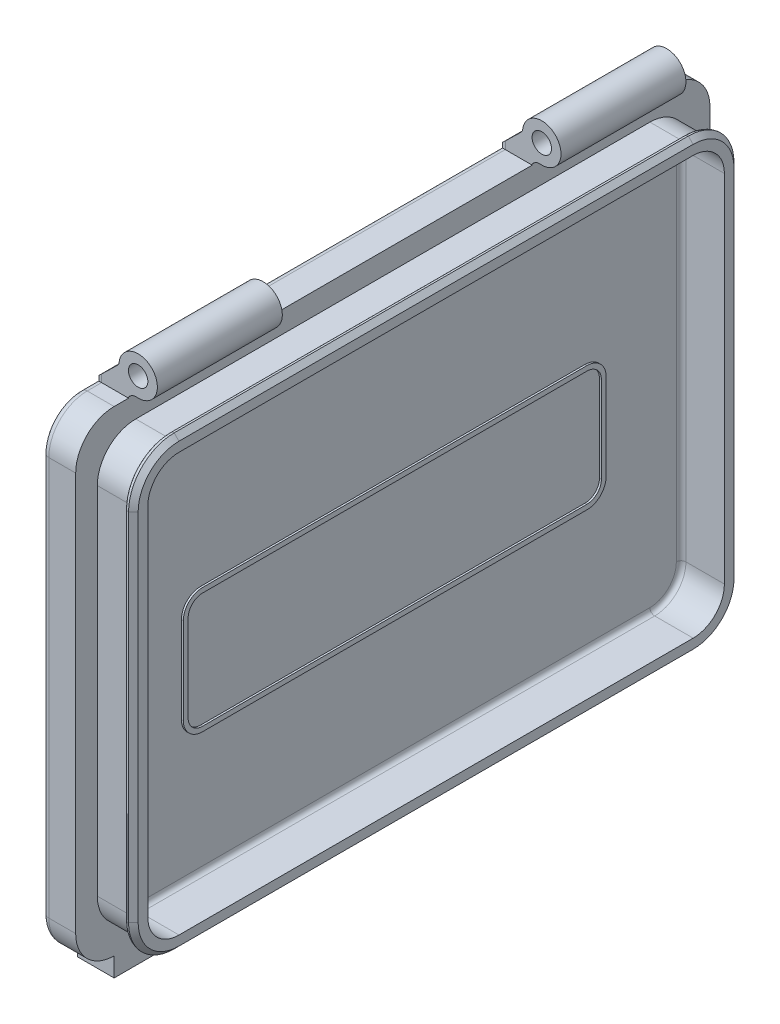
SolidWorks part; units mm, degrees
ref_plane "Front Plane" through (0, 0, 0) normal (0, 0, 1) x (1, 0, 0)
ref_plane "Top Plane" through (0, 0, 0) normal (0, 1, 0) x (1, 0, 0)
ref_plane "Right Plane" through (0, 0, 0) normal (1, 0, 0) x (0, 0, -1)
sketch "Sketch1" plane through (0, 0, 0) normal (0, 0, 1) x (1, 0, 0)
  circle A0 centre (0, 0) radius 1
  dimension "D1" = 2
extrude "Boss-Extrude1" add sketch "Sketch1" along normal blind 27.5
sketch "Sketch2" plane through (0, 0, 27.5) normal (0, 0, 1) x (1, 0, 0)
  line L0 (0, -1) -> (0, -2.4) construction
  line L1 (0, -2.4) -> (-1, -2.4) construction
  line L2 (-1, -2.4) -> (-4.5, -2.4) construction
  line L3 (-2.1365, -0.0921) -> (-4.5, -2.4)
  line L4 (-4.5, -2.4) -> (-1, -2.4)
  arc A0 (0, -2) -> (-1.9887, 0.2125) centre (0, 0) ccw
  circle A1 centre (0, 0) radius 1 construction
  arc A2 (-1, -2.4) -> (0, -2) centre (-0.1964, -2.9589) cw
  arc A3 (-2.1365, -0.0921) -> (-1.9887, 0.2125) centre (-2.4858, 0.2656) ccw
  circle A4 centre (0, 0) radius 1.01
  dimension "D1" = 4
  dimension "D5" = 0.5
  dimension "D6" = 2.02
  dimension "D2" = 1.4
  dimension "D3" = 1
  dimension "D4" = 3.5
extrude "Boss-Extrude2" add sketch "Sketch2" against normal blind 13 separate body
sketch "Sketch3" plane through (0, -2.4, 0) normal (0, -1, 0) x (1, 0, 0)
  line L0 (-4.5, 14.5) -> (-1, 14.5) construction
  line L1 (-4.5, 27.5) -> (-1, 27.5)
  line L2 (-4.5, 27.5) -> (-4.5, 14.5)
  line L3 (-4.5, 14.5) -> (-1, 14.5)
  line L4 (-1, 27.5) -> (-1, 14.5)
extrude "Boss-Extrude3" add sketch "Sketch3" along normal blind 49.6
sketch "Sketch7" plane through (0, 0, 27.5) normal (0, 0, 1) x (1, 0, 0)
  line L1 (-1, -52) -> (-1, -2.4) construction
  line L2 (-1, -2.5) -> (-4.5, -2.5)
  line L3 (-4.5, -52) -> (-4.5, -2.4) construction
  line L4 (-4.5, -2.5) -> (-4.5, -52)
  line L5 (-4.5, -52) -> (-1, -52)
  line L6 (-1, -52) -> (-1, -2.5)
extrude "Boss-Extrude6" add sketch "Sketch7" along normal blind 5.5
sketch "Sketch8" plane through (0, 0, 14.5) normal (0, 0, -1) x (-1, 0, 0)
  line L0 (4.5, -2.5) -> (1, -2.5)
  line L1 (1, -2.5) -> (1, -52)
  line L2 (1, -52) -> (4.5, -52)
  line L3 (4.5, -52) -> (4.5, -2.5)
extrude "Boss-Extrude7" add sketch "Sketch8" along normal blind 14.5
fillet "Fillet2" radius 4 2 edges at (-2.75, -52, 33) (-2.75, -2.5, 33)
ref_plane "Plane1" through (0, 0, 0) normal (0, 0, -1) x (-1, 0, 0)
sketch "Sketch10" plane through (0, 0, 0) normal (0, 0, -1) x (-1, 0, 0)
  line L0 (1, -52) -> (1, -54)
  line L1 (1, -54) -> (4.8, -54)
  line L2 (4.8, -54) -> (4.8, -53)
  line L3 (4.8, -53) -> (3.8, -53)
  line L4 (3.8, -53) -> (3.8, -52)
  line L5 (1, -52) -> (4.5, -52) construction
  line L6 (3.8, -52) -> (1, -52)
  line L7 (1, -52) -> (1.002, -52.0348)
  dimension "D1" = 2
  dimension "D2" = 3.8
  dimension "D3" = 1
  dimension "D4" = 1
extrude "Boss-Extrude8" add sketch "Sketch10" against normal up to vertex (29 mm away) contours L4 L6 L0 L1 L2 L3 region at (-2.6879, -53.0758, 0) up to point (-1, -52, 29)
sketch "Sketch11" plane through (-1, 0, 0) normal (1, 0, 0) x (0, 0, -1)
  line L0 (0, -36.2098) -> (-20, -36.2098)
  line L1 (0, -2.365) -> (0, 2.365) construction
  line L2 (-22, -34.2098) -> (-22, -25.2098)
  line L3 (-20, -23.2098) -> (0, -23.2098)
  line L4 (0, -23.2098) -> (0, -23.7098)
  line L5 (-21.5, -29.7098) -> (-21.5139, -29.7098) construction
  line L6 (-0.5, -35.7098) -> (-20, -35.7098)
  line L7 (-21.5, -34.2098) -> (-21.5, -25.2098)
  line L8 (-20, -23.7098) -> (-0.5, -23.7098)
  line L9 (-0.5, -35.7098) -> (0, -35.7098)
  line L10 (-0.5, -23.7098) -> (0, -23.7098)
  line L11 (0, -35.7098) -> (0, -36.2098)
  line L12 (-0.5, -23.7098) -> (-0.5, -35.7098) construction
  line L14 (0, -23.2098) -> (0, -36.2098) construction
  arc A0 (-22, -25.2098) -> (-20, -23.2098) centre (-20, -25.2098) cw
  arc A1 (-20, -36.2098) -> (-22, -34.2098) centre (-20, -34.2098) cw
  arc A2 (-20, -35.7098) -> (-21.5, -34.2098) centre (-20, -34.2098) cw
  arc A3 (-21.5, -25.2098) -> (-20, -23.7098) centre (-20, -25.2098) cw
  dimension "D3" = 2
  dimension "D1" = 13
  dimension "D2" = 22
  dimension "D4" = 0.5
extrude "Boss-Extrude9" add sketch "Sketch11" along normal blind 0.2
sketch "Sketch12" plane through (-1, 0, 0) normal (1, 0, 0) x (0, 0, -1)
  line L0 (0, -23.7098) -> (0, -35.7098) construction
  line L1 (0, -35.7098) -> (-20, -35.7098) construction
  line L2 (-21.5, -34.2098) -> (-21.5, -25.2098) construction
  line L3 (-20, -23.7098) -> (0, -23.7098) construction
  line L4 (0, -23.7098) -> (0, -35.7098)
  line L5 (0, -35.7098) -> (-20, -35.7098)
  line L6 (-21.5, -34.2098) -> (-21.5, -25.2098)
  line L7 (-20, -23.7098) -> (0, -23.7098)
  arc A0 (-21.5, -34.2098) -> (-20, -35.7098) centre (-20, -34.2098) ccw construction
  arc A1 (-20, -23.7098) -> (-21.5, -25.2098) centre (-20, -25.2098) ccw construction
  arc A2 (-21.5, -34.2098) -> (-20, -35.7098) centre (-20, -34.2098) ccw
  arc A3 (-20, -23.7098) -> (-21.5, -25.2098) centre (-20, -25.2098) ccw
sketch "Sketch13" plane through (-1, 0, 0) normal (1, 0, 0) x (0, 0, -1)
  line L1 (-29, -52) -> (0, -52) construction
  line L2 (0, -2.5) -> (0, -52) construction
  line L3 (0, -27.25) -> (-18.6818, -27.25) construction
  line L4 (-26.75, -5.5) -> (-0.75, -5.5)
  line L5 (-26.75, -4.75) -> (0, -4.75)
  line L6 (-30.75, -8.75) -> (-30.75, -45.75)
  line L7 (-26.75, -49.75) -> (0, -49.75)
  line L8 (0, -4.75) -> (0, -5.5)
  line L9 (-0.75, -5.5) -> (0, -5.5)
  line L10 (-26.75, -49) -> (-0.75, -49)
  line L11 (-30, -8.75) -> (-30, -45.75)
  line L13 (-0.75, -5.5) -> (-0.75, -49) construction
  line L14 (-0.75, -49) -> (0, -49)
  line L16 (0, -49) -> (0, -49.75)
  line L17 (0, -4.75) -> (0, -49.75) construction
  arc A0 (-30.75, -45.75) -> (-26.75, -49.75) centre (-26.75, -45.75) ccw
  arc A1 (-26.75, -4.75) -> (-30.75, -8.75) centre (-26.75, -8.75) ccw
  arc A2 (-30, -45.75) -> (-26.75, -49) centre (-26.75, -45.75) ccw
  arc A3 (-26.75, -5.5) -> (-30, -8.75) centre (-26.75, -8.75) ccw
  dimension "D3" = 4
  dimension "D1" = 45
  dimension "D2" = 30.75
  dimension "D4" = 0.75
extrude "Boss-Extrude11" add sketch "Sketch13" along normal blind 3.5
sketch "Sketch14" plane through (2.5, 0, 0) normal (1, 0, 0) x (0, 0, -1)
  line L3 (0, -49) -> (-26.75, -49) construction
  line L4 (-30, -45.75) -> (-30, -8.75) construction
  line L5 (-26.75, -5.5) -> (0, -5.5) construction
  line L6 (0, -49) -> (-26.75, -49)
  line L7 (-30, -45.75) -> (-30, -8.75)
  line L8 (-26.75, -5.5) -> (0, -5.5)
  line L9 (0, -50.5) -> (-26.75, -50.5)
  line L10 (-31.5, -45.75) -> (-31.5, -8.75)
  line L11 (-26.75, -4) -> (0, -4)
  line L12 (0, -4) -> (0, -5.5)
  line L13 (0, -49) -> (0, -50.5)
  arc A2 (-30, -45.75) -> (-26.75, -49) centre (-26.75, -45.75) ccw construction
  arc A3 (-26.75, -5.5) -> (-30, -8.75) centre (-26.75, -8.75) ccw construction
  arc A4 (-30, -45.75) -> (-26.75, -49) centre (-26.75, -45.75) ccw
  arc A5 (-26.75, -5.5) -> (-30, -8.75) centre (-26.75, -8.75) ccw
  arc A6 (-31.5, -45.75) -> (-26.75, -50.5) centre (-26.75, -45.75) ccw
  arc A7 (-26.75, -4) -> (-31.5, -8.75) centre (-26.75, -8.75) ccw
  dimension "D1" = 1.5
extrude "Boss-Extrude12" add sketch "Sketch14" along normal blind 1
ref_plane "Plane2" through (0, 0, 0) normal (0, 0, -1) x (-1, 0, 0)
mirror "Mirror1" about plane through (0, 0, 0) normal (0, 0, -1) of "Boss-Extrude12", "Boss-Extrude11", "Boss-Extrude9", "Boss-Extrude8", "Fillet2", "Boss-Extrude7", "Boss-Extrude6", "Boss-Extrude3", "Boss-Extrude2", "Boss-Extrude1"
sketch "Sketch15" plane through (0, 0, -27.5) normal (0, 0, -1) x (-1, 0, 0)
  circle A0 centre (0, 0) radius 1
extrude "Cut-Extrude1" cut sketch "Sketch15" against normal through all
chamfer "Chamfer1" distance 0.5 angle 45 8 edges at (3.5, -27.25, -31.5) (3.5, -49.1088, -30.1088) (3.5, -50.5, 0) (3.5, -49.1088, 30.1088) (3.5, -27.25, 31.5) (3.5, -5.3912, 30.1088) (3.5, -4, 0) (3.5, -5.3912, -30.1088)
fillet "Fillet3" radius 0.5 8 edges at (2.5, -4, 0) (2.5, -5.3912, 30.1088) (2.5, -27.25, 31.5) (2.5, -49.1088, 30.1088) (2.5, -50.5, 0) (2.5, -49.1088, -30.1088) (2.5, -27.25, -31.5) (2.5, -5.3912, -30.1088)
fillet "Fillet4" radius 0.5 5 edges at (-1, -6.4519, 29.0481) (-1, -27.25, 30) (-1, -48.0481, 29.0481) (-1, -49, 0) (-1, -5.5, 0)
fillet "Fillet6" radius 0.7 16 edges at (-4.5, -50.8284, -31.8284) (-4.5, -27.25, -33) (-4.5, -3.6716, -31.8284) (-4.5, -2.5, -28.25) (-4.5, -2.45, -27.5) (-4.5, -2.4, -21) (-4.5, -2.45, -14.5) (-4.5, -2.5, 0) (-4.5, -2.45, 14.5) (-4.5, -2.4, 21) (-4.5, -2.45, 27.5) (-4.5, -2.5, 28.25) (-4.5, -3.6716, 31.8284) (-4.5, -27.25, 33) (-4.5, -50.8284, 31.8284) (-4.5, -52, 0)
